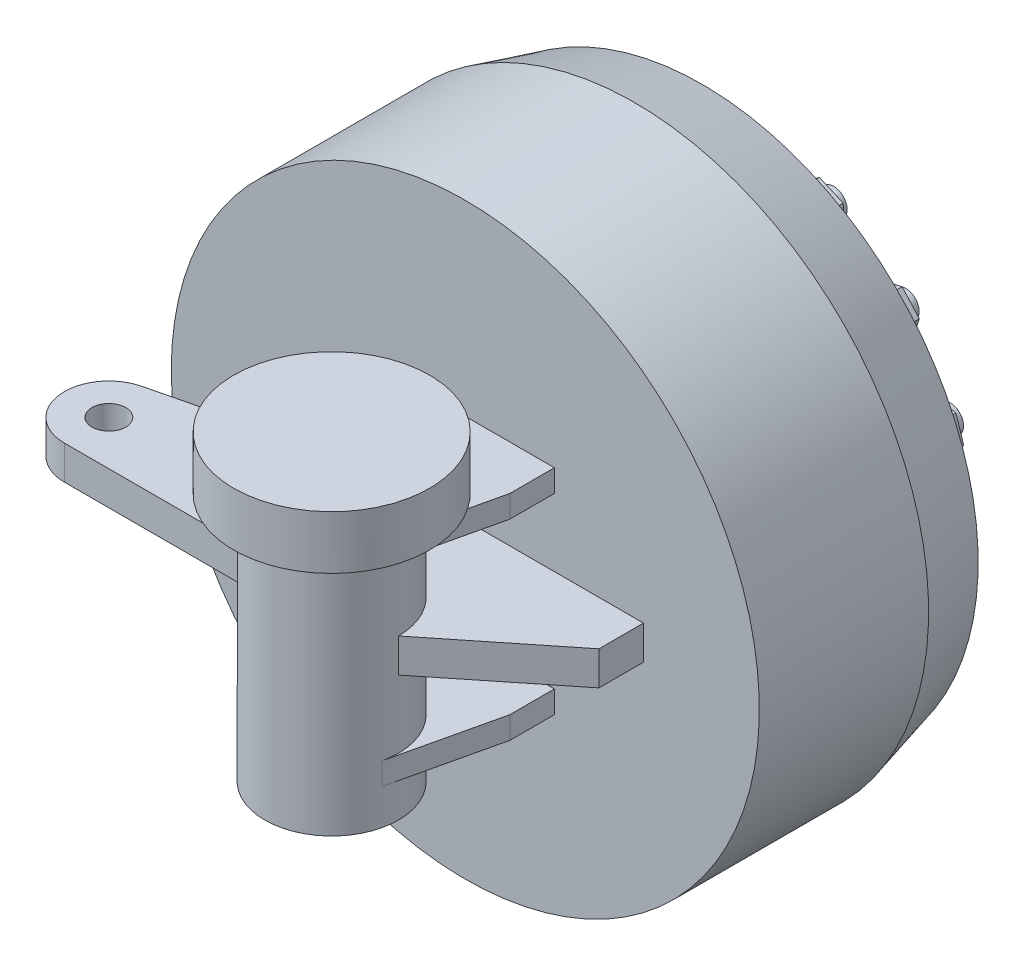
SolidWorks part; units mm, degrees
ref_plane "Front Plane" through (0, 0, 0) normal (0, 0, 1) x (1, 0, 0)
ref_plane "Top Plane" through (0, 0, 0) normal (0, 1, 0) x (1, 0, 0)
ref_plane "Right Plane" through (0, 0, 0) normal (1, 0, 0) x (0, 0, -1)
sketch "Sketch1" plane through (0, 0, 0) normal (1, 0, 0) x (0, 0, -1)
  line L0 (0, 0) -> (0, 165)
  line L1 (0, 165) -> (95, 165)
  line L2 (95, 165) -> (133, 154.8179)
  line L3 (133, 154.8179) -> (133, 75)
  line L4 (133, 75) -> (158, 75)
  line L5 (158, 75) -> (158, 50)
  line L6 (158, 50) -> (183, 50)
  line L7 (183, 50) -> (183, 0)
  line L8 (183, 0) -> (0, 0)
  dimension "D1" = 165
  dimension "D2" = 95
  dimension "D3" = 15
  dimension "D4" = 38
  dimension "D5" = 25
  dimension "D6" = 25
  dimension "D7" = 25
  dimension "D8" = 50
revolve "Revolve1" add sketch "Sketch1" angle 360 about L8
chamfer "Chamfer1" distance 4 angle 45 1 edges at (-50, 0, -183)
fillet "Fillet1" radius 3.5 1 edges at (-50, 0, -158)
fillet "Fillet2" radius 3.5 1 edges at (-75, 0, -158)
sketch "Sketch2" plane through (0, 0, 0) normal (0, 1, 0) x (1, 0, 0)
  circle A0 centre (0, -75) radius 37.5
  dimension "D1" = 75
  dimension "D2" = 75
extrude "Boss-Extrude1" add sketch "Sketch2" along normal blind 90 and the other way blind 80 separate body
sketch "Sketch3" plane through (0, 0, 0) normal (0, 1, 0) x (1, 0, 0)
  line L0 (-50, 0) -> (50, 0)
  line L1 (-165, 0) -> (165, 0) construction
  line L2 (50, 0) -> (50, -25)
  line L3 (50, -25) -> (36.543, -83.418)
  line L4 (0, 0) -> (0, -122.9435) construction
  line L5 (-50, -25) -> (-36.543, -83.418)
  line L6 (-50, 0) -> (-50, -25)
  line L7 (-36.543, -83.418) -> (36.543, -83.418)
  circle A0 centre (0, -75) radius 37.5 construction
  dimension "D1" = 50
  dimension "D2" = 25
extrude "Boss-Extrude2" add sketch "Sketch3" against normal blind 12.5 from offset 60
mirror "Mirror1" about plane through (0, 0, 0) normal (0, 1, 0) of "Boss-Extrude2"
sketch "Sketch4" plane through (0, 0, 0) normal (0, 1, 0) x (1, 0, 0)
  line L0 (-50, 0) -> (100, 0)
  line L1 (-165, 0) -> (165, 0) construction
  line L2 (100, 0) -> (100, -25)
  line L3 (0, -75) -> (157.0485, -75) construction
  line L4 (100, -25) -> (37.5, -75)
  line L5 (-37.5, -75) -> (-150, -75)
  line L6 (-155.8972, -25.7055) -> (-50, 0)
  circle A0 centre (0, -75) radius 37.5 construction
  arc A1 (36.543, -83.418) -> (-36.543, -83.418) centre (0, -75) ccw construction
  arc A2 (-150, -75) -> (-155.8972, -25.7055) centre (-150, -50) cw
  arc A3 (-37.5, -75) -> (37.5, -75) centre (0, -75) cw
  circle A4 centre (-150, -50) radius 9.5
  dimension "D1" = 150
  dimension "D5" = 25
  dimension "D6" = 19
  dimension "D2" = 25
  dimension "D3" = 100
  dimension "D4" = 150
extrude "Boss-Extrude3" add sketch "Sketch4" along normal mid plane 19
sketch "Sketch6" plane through (0, 60, 0) normal (0, 1, 0) x (1, 0, 0)
  circle A0 centre (0, -75) radius 55
  dimension "D1" = 110
extrude "Boss-Extrude4" add sketch "Sketch6" along normal up to surface (30 mm away) up to face at (0, 90, 112.5)
sketch "Sketch7" plane through (0, 0, -133) normal (0, 0, -1) x (-1, 0, 0)
  line L0 (61.9943, 103.7547) -> (60.4856, 118.1094)
  line L1 (7.2169, 132.5) -> (-7.2169, 132.5)
  line L2 (-7.2169, 132.5) -> (-14.4338, 120)
  line L3 (-14.4338, 120) -> (-7.2169, 107.5)
  line L4 (-7.2169, 107.5) -> (7.2169, 107.5)
  line L5 (7.2169, 107.5) -> (14.4338, 120)
  line L6 (14.4338, 120) -> (7.2169, 132.5)
  line L7 (60.4856, 118.1094) -> (47.2997, 123.9801)
  line L8 (47.2997, 123.9801) -> (35.6225, 115.4962)
  line L9 (35.6225, 115.4962) -> (37.1312, 101.1415)
  line L10 (37.1312, 101.1415) -> (50.3171, 95.2708)
  line L11 (50.3171, 95.2708) -> (61.9943, 103.7547)
  line L12 (98.8354, 69.5693) -> (103.2957, 83.2966)
  line L13 (103.2957, 83.2966) -> (93.6377, 94.023)
  line L14 (93.6377, 94.023) -> (79.5193, 91.022)
  line L15 (79.5193, 91.022) -> (75.059, 77.2947)
  line L16 (75.059, 77.2947) -> (84.7171, 66.5684)
  line L17 (84.7171, 66.5684) -> (98.8354, 69.5693)
  line L18 (118.5871, 23.3547) -> (128.2451, 34.0811)
  line L19 (128.2451, 34.0811) -> (123.7849, 47.8084)
  line L20 (123.7849, 47.8084) -> (109.6665, 50.8094)
  line L21 (109.6665, 50.8094) -> (100.0084, 40.083)
  line L22 (100.0084, 40.083) -> (104.4687, 26.3557)
  line L23 (104.4687, 26.3557) -> (118.5871, 23.3547)
  line L24 (117.8339, -26.8981) -> (131.0198, -21.0274)
  line L25 (131.0198, -21.0274) -> (132.5285, -6.6727)
  line L26 (132.5285, -6.6727) -> (120.8514, 1.8113)
  line L27 (120.8514, 1.8113) -> (107.6655, -4.0595)
  line L28 (107.6655, -4.0595) -> (106.1567, -18.4142)
  line L29 (106.1567, -18.4142) -> (117.8339, -26.8981)
  line L30 (96.7062, -72.5) -> (111.1399, -72.5)
  line L31 (111.1399, -72.5) -> (118.3568, -60)
  line L32 (118.3568, -60) -> (111.1399, -47.5)
  line L33 (111.1399, -47.5) -> (96.7062, -47.5)
  line L34 (96.7062, -47.5) -> (89.4893, -60)
  line L35 (89.4893, -60) -> (96.7062, -72.5)
  line L36 (58.8571, -105.566) -> (72.043, -111.4367)
  line L37 (72.043, -111.4367) -> (83.7201, -102.9528)
  line L38 (83.7201, -102.9528) -> (82.2114, -88.5981)
  line L39 (82.2114, -88.5981) -> (69.0255, -82.7274)
  line L40 (69.0255, -82.7274) -> (57.3483, -91.2113)
  line L41 (57.3483, -91.2113) -> (58.8571, -105.566)
  line L42 (10.8311, -120.3787) -> (20.4891, -131.105)
  line L43 (20.4891, -131.105) -> (34.6075, -128.1041)
  line L44 (34.6075, -128.1041) -> (39.0677, -114.3768)
  line L45 (39.0677, -114.3768) -> (29.4097, -103.6504)
  line L46 (29.4097, -103.6504) -> (15.2913, -106.6513)
  line L47 (15.2913, -106.6513) -> (10.8311, -120.3787)
  line L48 (-39.0677, -114.3768) -> (-34.6075, -128.1041)
  line L49 (-34.6075, -128.1041) -> (-20.4891, -131.105)
  line L50 (-20.4891, -131.105) -> (-10.8311, -120.3787)
  line L51 (-10.8311, -120.3787) -> (-15.2913, -106.6513)
  line L52 (-15.2913, -106.6513) -> (-29.4097, -103.6504)
  line L53 (-29.4097, -103.6504) -> (-39.0677, -114.3768)
  line L54 (-82.2114, -88.5981) -> (-83.7201, -102.9528)
  line L55 (-83.7201, -102.9528) -> (-72.043, -111.4367)
  line L56 (-72.043, -111.4367) -> (-58.8571, -105.566)
  line L57 (-58.8571, -105.566) -> (-57.3483, -91.2113)
  line L58 (-57.3483, -91.2113) -> (-69.0255, -82.7274)
  line L59 (-69.0255, -82.7274) -> (-82.2114, -88.5981)
  line L60 (-111.1399, -47.5) -> (-118.3568, -60)
  line L61 (-118.3568, -60) -> (-111.1399, -72.5)
  line L62 (-111.1399, -72.5) -> (-96.7062, -72.5)
  line L63 (-96.7062, -72.5) -> (-89.4893, -60)
  line L64 (-89.4893, -60) -> (-96.7062, -47.5)
  line L65 (-96.7062, -47.5) -> (-111.1399, -47.5)
  line L66 (-120.8514, 1.8113) -> (-132.5285, -6.6727)
  line L67 (-132.5285, -6.6727) -> (-131.0198, -21.0274)
  line L68 (-131.0198, -21.0274) -> (-117.8339, -26.8981)
  line L69 (-117.8339, -26.8981) -> (-106.1567, -18.4142)
  line L70 (-106.1567, -18.4142) -> (-107.6655, -4.0595)
  line L71 (-107.6655, -4.0595) -> (-120.8514, 1.8113)
  line L72 (-109.6665, 50.8094) -> (-123.7849, 47.8084)
  line L73 (-123.7849, 47.8084) -> (-128.2451, 34.0811)
  line L74 (-128.2451, 34.0811) -> (-118.5871, 23.3547)
  line L75 (-118.5871, 23.3547) -> (-104.4687, 26.3557)
  line L76 (-104.4687, 26.3557) -> (-100.0084, 40.083)
  line L77 (-100.0084, 40.083) -> (-109.6665, 50.8094)
  line L78 (-79.5193, 91.022) -> (-93.6377, 94.023)
  line L79 (-93.6377, 94.023) -> (-103.2957, 83.2966)
  line L80 (-103.2957, 83.2966) -> (-98.8354, 69.5693)
  line L81 (-98.8354, 69.5693) -> (-84.7171, 66.5684)
  line L82 (-84.7171, 66.5684) -> (-75.059, 77.2947)
  line L83 (-75.059, 77.2947) -> (-79.5193, 91.022)
  line L84 (-35.6225, 115.4962) -> (-47.2997, 123.9801)
  line L85 (-47.2997, 123.9801) -> (-60.4856, 118.1094)
  line L86 (-60.4856, 118.1094) -> (-61.9943, 103.7547)
  line L87 (-61.9943, 103.7547) -> (-50.3171, 95.2708)
  line L88 (-50.3171, 95.2708) -> (-37.1312, 101.1415)
  line L89 (-37.1312, 101.1415) -> (-35.6225, 115.4962)
  circle A0 centre (0, 120) radius 12.5 construction
  circle A1 centre (0, 120) radius 7.5
  circle A2 centre (48.8084, 109.6255) radius 7.5
  circle A3 centre (48.8084, 109.6255) radius 12.5 construction
  circle A4 centre (89.1774, 80.2957) radius 7.5
  circle A5 centre (89.1774, 80.2957) radius 12.5 construction
  circle A6 centre (114.1268, 37.082) radius 7.5
  circle A7 centre (114.1268, 37.082) radius 12.5 construction
  circle A8 centre (119.3426, -12.5434) radius 7.5
  circle A9 centre (119.3426, -12.5434) radius 12.5 construction
  circle A10 centre (103.923, -60) radius 7.5
  circle A11 centre (103.923, -60) radius 12.5 construction
  circle A12 centre (70.5342, -97.082) radius 7.5
  circle A13 centre (70.5342, -97.082) radius 12.5 construction
  circle A14 centre (24.9494, -117.3777) radius 7.5
  circle A15 centre (24.9494, -117.3777) radius 12.5 construction
  circle A16 centre (-24.9494, -117.3777) radius 7.5
  circle A17 centre (-24.9494, -117.3777) radius 12.5 construction
  circle A18 centre (-70.5342, -97.082) radius 7.5
  circle A19 centre (-70.5342, -97.082) radius 12.5 construction
  circle A20 centre (-103.923, -60) radius 7.5
  circle A21 centre (-103.923, -60) radius 12.5 construction
  circle A22 centre (-119.3426, -12.5434) radius 7.5
  circle A23 centre (-119.3426, -12.5434) radius 12.5 construction
  circle A24 centre (-114.1268, 37.082) radius 7.5
  circle A25 centre (-114.1268, 37.082) radius 12.5 construction
  circle A26 centre (-89.1774, 80.2957) radius 7.5
  circle A27 centre (-89.1774, 80.2957) radius 12.5 construction
  circle A28 centre (-48.8084, 109.6255) radius 7.5
  circle A29 centre (-48.8084, 109.6255) radius 12.5 construction
  circle A30 centre (0, 0) radius 120 construction
  point P138 (0, 0)
  point P140 (92.7992, 80.5068)
  point P141 (0, 0)
  dimension "D2" = 15
  dimension "D1" = 25
  dimension "D3" = 120
  dimension "D4" = 15
extrude "Boss-Extrude5" add sketch "Sketch7" along normal blind 25 contours A20 | A22 | A18 | A16 | A12 | A10 | A8 | A6 | A4 | A2 | A28 | A26 | A24 | A1 | A14 region at (-48.8084, 109.6255, -133) region at (-89.1774, 80.2957, -133) region at (-114.1268, 37.082, -133) region at (-119.3426, -12.5434, -133) region at (-103.923, -60, -133) region at (-70.5342, -97.082, -133) region at (24.9494, -117.3777, -133) region at (70.5342, -97.082, -133) region at (103.923, -60, -133) region at (119.3426, -12.5434, -133) region at (114.1268, 37.082, -133) region at (89.1774, 80.2957, -133) region at (48.8084, 109.6255, -133)
extrude "Boss-Extrude6" add sketch "Sketch7<3>" along normal blind 12.5 from offset 6
sketch "Sketch7<3>" plane through (0, 0, -133) normal (0, 0, -1) x (-1, 0, 0) same geometry as "Sketch7"
